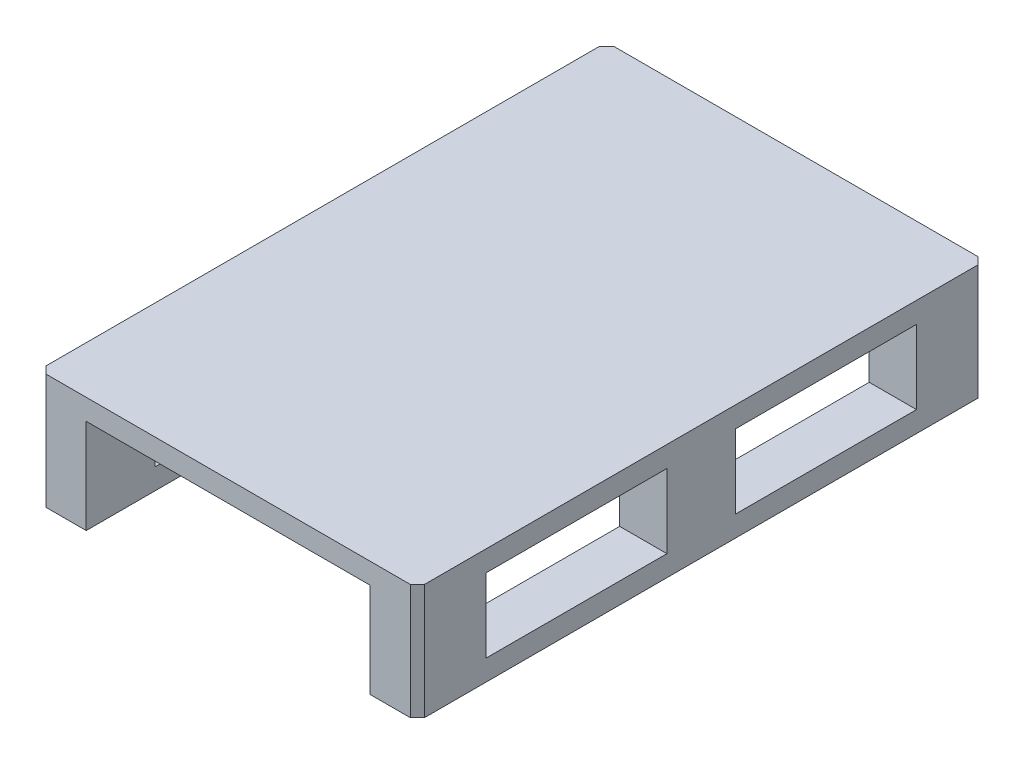
SolidWorks part; units mm, degrees
material "PLA"
ref_plane "Piano frontale" through (0, 0, 0) normal (0, 0, 1) x (1, 0, 0)
ref_plane "Piano superiore" through (0, 0, 0) normal (0, 1, 0) x (1, 0, 0)
ref_plane "Piano destro" through (0, 0, 0) normal (1, 0, 0) x (0, 0, -1)
sketch "Schizzo1" plane through (0, 0, 0) normal (1, 0, 0) x (0, 0, -1)
  line L0 (0, 0) -> (0, 7.2)
  line L1 (0, 7.2) -> (60, 7.2)
  line L2 (60, 7.2) -> (60, 0)
  line L3 (60, 0) -> (0, 0)
  line L8 (33.625, 6.1) -> (33.625, 1.1)
  line L9 (33.625, 1.1) -> (52.75, 1.1)
  line L10 (52.75, 1.1) -> (52.75, 6.1)
  line L11 (52.75, 6.1) -> (33.625, 6.1)
  line L12 (30, 7.2) -> (30, 0) construction
  line L13 (7.25, 1.1) -> (7.25, 6.1)
  line L14 (26.375, 1.1) -> (7.25, 1.1)
  line L15 (26.375, 6.1) -> (26.375, 1.1)
  line L16 (7.25, 6.1) -> (26.375, 6.1)
  dimension "D1" = 7.2
  dimension "D2" = 7.25
  dimension "D3" = 5
  dimension "D4" = 7.25
  dimension "D5" = 60
  dimension "D6" = 1.1
extrude "Estrusione-Estrusione1" add sketch "Schizzo1" along normal blind 40
sketch "Schizzo2" plane through (0, 0, 0) normal (0, 0, 1) x (1, 0, 0)
  line L0 (5, 0) -> (5, 5)
  line L1 (40, 0) -> (0, 0) construction
  line L2 (5, 5) -> (16.375, 5)
  line L3 (16.375, 5) -> (16.375, 0)
  line L4 (16.375, 0) -> (5, 0)
  line L5 (20, 7.2) -> (20, 0) construction
  line L6 (40, 7.2) -> (0, 7.2) construction
  line L8 (0, 7.2) -> (0, 0) construction
  line L9 (23.625, 5) -> (23.625, 0)
  line L14 (14.3, 7.2) -> (16.375, 7.2)
  line L15 (14.3, 7.2) -> (14.3, 6.1)
  line L16 (14.3, 6.1) -> (16.375, 6.1)
  line L17 (16.375, 7.2) -> (16.375, 6.1)
  line L18 (7.25, 7.2) -> (9.3, 7.2)
  line L19 (7.25, 7.2) -> (7.25, 6.1)
  line L20 (7.25, 6.1) -> (9.3, 6.1)
  line L21 (9.3, 7.2) -> (9.3, 6.1)
  line L22 (35, 5) -> (23.625, 5)
  line L23 (35, 0) -> (35, 5)
  line L24 (23.625, 0) -> (35, 0)
  line L25 (25.7, 6.1) -> (23.625, 6.1)
  line L26 (23.625, 7.2) -> (23.625, 6.1)
  line L27 (25.7, 7.2) -> (23.625, 7.2)
  line L28 (25.7, 7.2) -> (25.7, 6.1)
  line L29 (32.75, 6.1) -> (30.7, 6.1)
  line L30 (30.7, 7.2) -> (30.7, 6.1)
  line L31 (32.75, 7.2) -> (30.7, 7.2)
  line L32 (32.75, 7.2) -> (32.75, 6.1)
  dimension "D1" = 5
  dimension "D2" = 3.625
  dimension "D3" = 2.2
  dimension "D4" = 1.1
  dimension "D5" = 7.25
  dimension "D6" = 3.625
  dimension "D7" = 21.4
  dimension "D8" = 1.1
  dimension "D9" = 5
extrude "Taglio-Estrusione1" cut sketch "Schizzo2" against normal through all
chamfer "Smusso1" distance 0.75 angle 45 4 edges at (0, 3.6, -60) (40, 3.6, -60) (40, 3.6, 0) (0, 3.6, 0)
sketch "Schizzo3" plane through (0, 0, 0) normal (0, 0, 1) x (1, 0, 0)
  line L1 (16.375, 0) -> (23.625, 0)
  line L2 (16.375, 0) -> (16.375, 5)
  line L3 (16.375, 5) -> (23.625, 5)
  line L4 (23.625, 0) -> (23.625, 5)
extrude "Taglio-Estrusione2" cut sketch "Schizzo3" against normal blind 64
sketch "Schizzo4" plane through (0, 0, 0) normal (0, 0, 1) x (1, 0, 0)
  line L6 (39.25, 0) -> (39.25, 7.2) construction
  line L7 (0.75, 7.2) -> (39.25, 7.2)
  line L8 (0.75, 7.2) -> (0.75, 6.1)
  line L9 (0.75, 6.1) -> (39.25, 6.1)
  line L10 (39.25, 7.2) -> (39.25, 6.1)
  dimension "D1" = 1.1
extrude "Estrusione-Estrusione3" add sketch "Schizzo4" against normal blind 60
sketch "Schizzo7" plane through (0, 0, -52.75) normal (0, 0, 1) x (1, 0, 0)
  line L0 (40, 6.1) -> (0, 6.1) construction
  line L1 (35, 5) -> (5, 5)
  line L2 (35, 5) -> (35, 6.1)
  line L3 (35, 6.1) -> (5, 6.1)
  line L4 (5, 5) -> (5, 6.1)
  point P7 (0, 0)
extrude "Estrusione-Estrusione4" add sketch "Schizzo7" along normal blind 50
sketch "Schizzo8" plane through (0, 0, 0) normal (0, -1, 0) x (1, 0, 0)
  line L0 (5, 0) -> (0.75, 0)
  line L1 (0.75, 0) -> (0, -0.75)
  line L2 (0, -0.75) -> (0, -59.25)
  line L3 (0, -59.25) -> (0.75, -60)
  line L4 (0.75, -60) -> (5, -60)
  line L5 (5, -60) -> (5, 0)
  line L6 (35, 0) -> (35, -60)
  line L7 (35, -60) -> (39.25, -60)
  line L8 (39.25, -60) -> (40, -59.25)
  line L9 (40, -59.25) -> (40, -0.75)
  line L10 (40, -0.75) -> (39.25, 0)
  line L11 (39.25, 0) -> (35, 0)
extrude "Estrusione-Estrusione5" add sketch "Schizzo8" along normal blind 5
sketch "Schizzo9" plane through (35, 0, 0) normal (1, 0, 0) x (0, 0, -1)
  line L1 (7.25, 6.1) -> (26.375, 6.1)
  line L2 (7.25, 6.1) -> (7.25, 5)
  line L3 (7.25, 5) -> (26.375, 5)
  line L4 (26.375, 6.1) -> (26.375, 5)
  line L5 (33.625, 6.1) -> (52.75, 6.1)
  line L6 (33.625, 6.1) -> (33.625, 5)
  line L7 (33.625, 5) -> (52.75, 5)
  line L8 (52.75, 6.1) -> (52.75, 5)
extrude "Estrusione-Estrusione6" add sketch "Schizzo9" along normal blind 5 and the other way blind 35
sketch "Schizzo10" plane through (0, 0, 0) normal (-1, 0, 0) x (0, 0, 1)
  line L1 (-52.75, 1.1) -> (-33.625, 1.1)
  line L2 (-52.75, 1.1) -> (-52.75, -2.8)
  line L3 (-52.75, -2.8) -> (-33.625, -2.8)
  line L4 (-33.625, 1.1) -> (-33.625, -2.8)
  line L5 (-26.375, 1.1) -> (-7.25, 1.1)
  line L6 (-26.375, 1.1) -> (-26.375, -2.8)
  line L7 (-26.375, -2.8) -> (-7.25, -2.8)
  line L8 (-7.25, 1.1) -> (-7.25, -2.8)
  line L10 (-33.625, 5) -> (-52.75, 5) construction
  line L11 (-7.25, 5) -> (-26.375, 5) construction
  dimension "D1" = 3.9
extrude "Taglio-Estrusione3" cut sketch "Schizzo10" against normal through all
